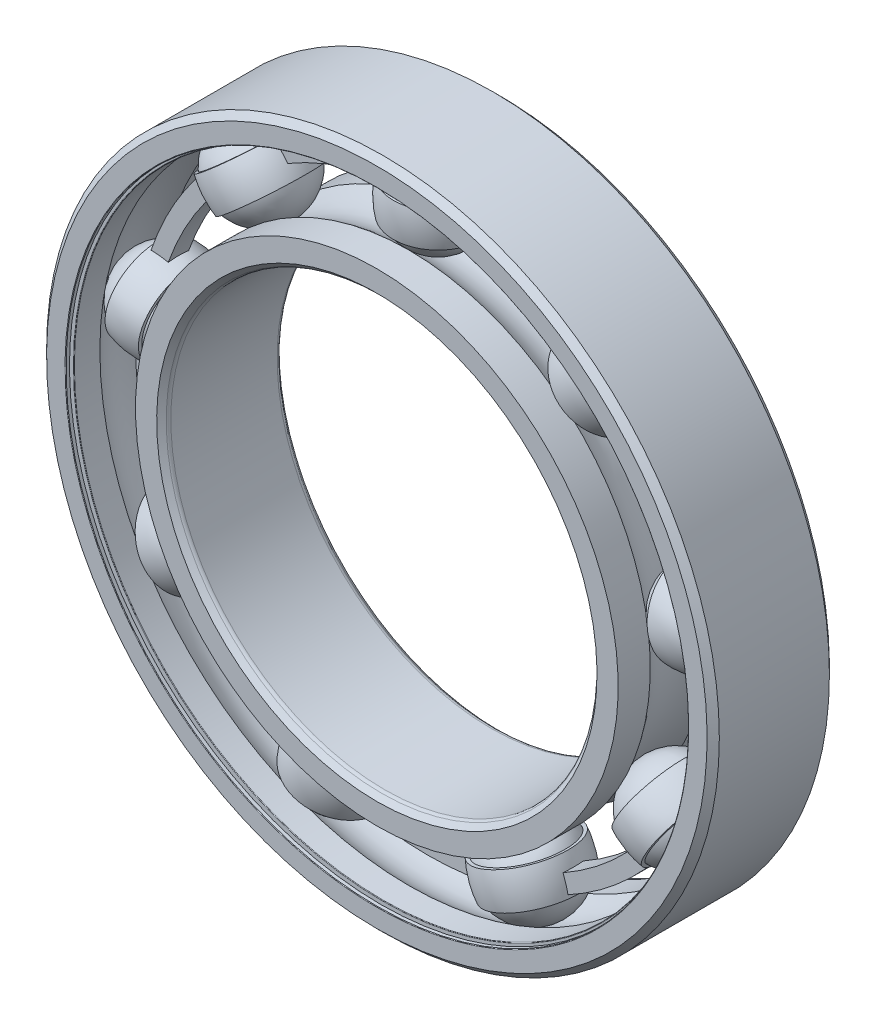
SolidWorks part; units mm, degrees
ref_plane "Front Plane" through (0, 0, 0) normal (0, 0, 1) x (1, 0, 0)
ref_plane "Top Plane" through (0, 0, 0) normal (0, 1, 0) x (1, 0, 0)
ref_plane "Right Plane" through (0, 0, 0) normal (1, 0, 0) x (0, 0, -1)
sketch "Sketch1" plane through (0, 0, 0) normal (0, 0, 1) x (1, 0, 0)
  line L0 (-27.5, 0) -> (27.5, 0) construction
  line L1 (-17.4995, 0) -> (17.4995, 0) construction
  circle A0 centre (0, 0) radius 17.4995 construction
  circle A1 centre (0, 0) radius 27.5 construction
  point P3 (0, 0)
  point P6 (0, 0)
  point P7 (0, -17.4995)
  point P11 (0, -27.5)
  point P12 (0, 17.4995)
  point P13 (0, 27.5)
  dimension "OD" = 55
  dimension "ID" = 34.999
sketch "Sketch2" plane through (0, 0, 0) normal (1, 0, 0) x (0, 0, -1)
  line L0 (-5, 27.5) -> (5, 27.5) construction
  line L1 (0, 27.5) -> (0, -27.5) construction
  line L2 (4.5, 27.5) -> (-4.5, 27.5)
  line L3 (-4.5, 27.5) -> (-5, 27)
  line L4 (-5, 27) -> (-5, 25.269)
  line L5 (-5, 25.269) -> (-2.375, 25.269)
  line L6 (5, 25.269) -> (2.375, 25.269)
  line L7 (5, 27) -> (5, 25.269)
  line L8 (4.5, 27.5) -> (5, 27)
  line L9 (0, 27.5) -> (0, 22.4997) construction
  line L10 (0, 22.4997) -> (0, 17.4995) construction
  line L11 (0, 27.5) -> (0, -27.5) construction
  line L12 (-5, 0) -> (5, 0) construction
  line L13 (5, 17.4995) -> (-5, 17.4995) construction
  line L14 (0, 26.1479) -> (0, 18.8516) construction
  line L15 (-5, -17.4995) -> (5, -17.4995) construction
  line L16 (-5, -17.5) -> (-5, 17.5) construction
  line L17 (5, 27.5) -> (5, -27.5) construction
  arc A0 (-2.375, 25.269) -> (2.375, 25.269) centre (0, 22.4997) cw
  circle A1 centre (0, 22.4997) radius 3.6482 construction
  point P14 (0, 17.4995)
  point P17 (0, 0)
  point P21 (0, 27.5)
  point P29 (0, 17.4995)
  point P30 (0, -17.4995)
  point P35 (0, 26.1479)
  dimension "Approx. Ball Dia." = 7.2964
  dimension "Width" = 10
  dimension "D1" = 45
  dimension "D2" = 0.5
  dimension "D3" = 4.75
  dimension "D4" = 2.7692
  dimension "For Shaft Diameter" = 35
  dimension "For Housing ID" = 55
sketch "Sketch3" plane through (0, 0, 0) normal (1, 0, 0) x (0, 0, -1)
  line L0 (4.5, 27.5) -> (5, 27) construction
  line L1 (5, 27) -> (5, 25.269) construction
  line L2 (5, 25.269) -> (2.375, 25.269) construction
  line L3 (-5, 25.269) -> (-2.375, 25.269) construction
  line L4 (-5, 27) -> (-5, 25.269) construction
  line L5 (-4.5, 27.5) -> (-5, 27) construction
  line L6 (4.5, 27.5) -> (-4.5, 27.5) construction
  line L7 (4.5, 27.5) -> (5, 27)
  line L8 (5, 27) -> (5, 25.269)
  line L9 (5, 25.269) -> (2.375, 25.269)
  line L10 (-5, 25.269) -> (-2.375, 25.269)
  line L11 (-5, 27) -> (-5, 25.269)
  line L12 (-4.5, 27.5) -> (-5, 27)
  line L13 (4.5, 27.5) -> (-4.5, 27.5)
  arc A0 (2.375, 25.269) -> (-2.375, 25.269) centre (0, 22.4997) ccw construction
  arc A1 (2.375, 25.269) -> (-2.375, 25.269) centre (0, 22.4997) ccw
revolve "Revolve1" add sketch "Sketch3" angle 360 about L12
sketch "Sketch8" plane through (0, 0, 0) normal (1, 0, 0) x (0, 0, -1)
  line L0 (-5, 25.269) -> (-2.375, 25.269) construction
  line L1 (-4.68, 25.269) -> (-4.5, 25.269)
  line L2 (-4.68, 25.269) -> (-4.68, 26.0127) construction
  line L3 (-4.68, 26.0127) -> (-4.5, 26.0127)
  line L4 (-4.5, 25.269) -> (-4.5, 26.0127)
  line L5 (5, 25.269) -> (2.375, 25.269) construction
  line L6 (4.5, 25.269) -> (4.68, 25.269)
  line L7 (4.5, 25.269) -> (4.5, 26.0127)
  line L8 (4.5, 26.0127) -> (4.68, 26.0127)
  line L9 (4.68, 25.269) -> (4.68, 26.0127) construction
  line L10 (-4.5, 26.0127) -> (4.5, 26.0127) construction
  line L11 (0, 27.5) -> (0, -27.5) construction
  line L12 (-4.68, 26.0127) -> (-4.68, 26.7563) construction
  line L13 (-4.68, 26.7563) -> (-4.68, 27.5) construction
  line L14 (-5, 27.5) -> (5, 27.5) construction
  line L15 (-4.68, 25.269) -> (-5, 25.269)
  line L16 (-5, 25.269) -> (-5, 25.449)
  line L17 (-5, 27) -> (-5, 25.269) construction
  line L18 (-5, 25.449) -> (-4.68, 25.449)
  line L19 (-4.68, 25.449) -> (-4.68, 26.0127)
  line L20 (4.68, 25.269) -> (5, 25.269)
  line L21 (5, 25.269) -> (5, 25.449)
  line L22 (5, 27) -> (5, 25.269) construction
  line L23 (5, 25.449) -> (4.68, 25.449)
  line L24 (4.68, 25.449) -> (4.68, 26.0127)
  point P12 (0, 26.0127)
  dimension "D1" = 9
  dimension "D2" = 0.18
revolve "Cut-Revolve1" cut sketch "Sketch8" angle 360 about L12
sketch "Sketch4" plane through (0, 0, 0) normal (1, 0, 0) x (0, 0, -1)
  line L0 (0, 27.5) -> (0, -27.5) construction
  line L1 (0, 27.5) -> (0, -27.5) construction
  line L2 (-4.5, 17.4995) -> (-5, 17.9995)
  line L3 (-5, 17.9995) -> (-5, 19.7305)
  line L5 (-5, 19.7305) -> (-2.375, 19.7305)
  line L6 (-4.5, 17.4995) -> (4.5, 17.4995)
  line L8 (4.5, 17.4995) -> (5, 17.9995)
  line L10 (5, 17.9995) -> (5, 19.7305)
  line L11 (5, 19.7305) -> (2.375, 19.7305)
  line L12 (-5, 27) -> (-5, 25.269) construction
  line L13 (4.5, 27.5) -> (5, 27) construction
  line L15 (5, -27) -> (5, 27) construction
  line L16 (4.5, 27.5) -> (4.5, -27.5) construction
  arc A1 (2.375, 19.7305) -> (-2.375, 19.7305) centre (0, 22.4997) cw
  circle A2 centre (0, 22.4997) radius 3.6482 construction
  point P1 (0, 17.4995)
revolve "Revolve2" add sketch "Sketch4" angle 360 about L12
sketch "Sketch5" plane through (0, 0, 0) normal (1, 0, 0) x (0, 0, -1)
  line L0 (-3.6482, 22.4997) -> (3.6482, 22.4997)
  arc A2 (-3.6482, 22.4997) -> (3.6482, 22.4997) centre (0, 22.4997) cw
  arc A3 (2.375, 25.269) -> (-2.375, 25.269) centre (0, 22.4997) ccw construction
revolve "Revolve3" add sketch "Sketch5" angle 360 about L0
sketch "Sketch6" plane through (0, 0, 0) normal (1, 0, 0) x (0, 0, -1)
  line L0 (-2.375, 25.269) -> (-2.375, 23.8844) construction
  line L1 (-2.375, 23.8844) -> (-2.375, 22.4997) construction
  line L2 (-2.375, 22.4997) -> (-2.375, 21.1151) construction
  line L3 (-2.375, 21.1151) -> (-2.375, 19.7305) construction
  line L4 (-5, 23.8844) -> (-4.7292, 23.8844) construction
  line L5 (-2.375, 23.8844) -> (-2.375, 21.1151) construction
  line L7 (-4.7292, 23.8844) -> (-4.4584, 23.8844) construction
  line L8 (-4.4584, 23.8844) -> (-4.1876, 23.8844) construction
  line L10 (0, 27.5) -> (0, -27.5) construction
  line L11 (0, 27.5) -> (0, -27.5) construction
  line L12 (-5, 25.269) -> (-5, 23.8844) construction
  line L13 (-3.646, 23.8844) -> (-3.3752, 23.8844) construction
  line L14 (-5, 27) -> (-5, -27) construction
  line L15 (-5, 23.8844) -> (-5, 22.4997) construction
  line L16 (-5, 22.4997) -> (-5, 21.1151) construction
  line L17 (-5, 21.1151) -> (-5, 19.7305) construction
  line L18 (-4.1876, 23.8844) -> (-3.9168, 23.8844) construction
  line L19 (-3.9168, 23.8844) -> (-3.646, 23.8844) construction
  line L20 (-3.3752, 23.8844) -> (-3.646, 23.8844)
  line L21 (-5, 21.1151) -> (-4.7292, 21.1151) construction
  line L22 (-4.7292, 21.1151) -> (-4.4584, 21.1151) construction
  line L23 (-4.4584, 21.1151) -> (-4.1876, 21.1151) construction
  line L24 (-4.1876, 21.1151) -> (-3.9168, 21.1151) construction
  line L25 (-3.9168, 21.1151) -> (-3.646, 21.1151) construction
  line L26 (-3.646, 21.1151) -> (-3.3752, 21.1151) construction
  line L27 (-3.3752, 21.1151) -> (-3.646, 21.1151)
  line L28 (-3.9168, 23.8844) -> (-3.9168, 21.1151) construction
  line L30 (-3.7814, 23.8844) -> (-3.7814, 21.1151) construction
  circle A0 centre (0, 22.4997) radius 3.6482 construction
  arc A2 (-3.646, 21.1151) -> (-3.646, 23.8844) centre (3.366, 22.4997) cw
  arc A3 (-3.3752, 23.8844) -> (-3.3752, 21.1151) centre (0, 22.4997) ccw
revolve "Revolve4" add sketch "Sketch6" angle 360 about L11
sketch "Sketch7" plane through (0, 0, 0) normal (0, 0, 1) x (1, 0, 0)
  line L0 (-3.6482, 22.4997) -> (3.6482, 22.4997) construction
  line L1 (0, 18.8516) -> (0, 26.1479) construction
  line L2 (0, 0) -> (7.6954, 21.1428) construction
  line L8 (0, 27.5) -> (0, -27.5) construction
  line L9 (14.4626, 17.2358) -> (15.3526, 18.2965)
  line L10 (0, 27.5) -> (0, -27.5) construction
  line L11 (0, 23.8844) -> (0, 22.4997)
  arc A1 (14.4626, 17.2358) -> (0, 22.4997) centre (0, 0) ccw
  arc A2 (15.3526, 18.2965) -> (0, 23.8844) centre (0, 0) ccw
  dimension "D1" = 40
  dimension "D2" = 7.2964
extrude "Boss-Extrude1" add sketch "Sketch7" along normal mid plane 1.6667
pattern_circular "CirPattern1" count 9 over 360 about axis through (0, 0, 5) along (0, 0, -1) of bodies 104 134
pattern_circular "CirPattern2" count 9 over 360 about axis through (0, 0, 5) along (0, 0, -1) of "Revolve4", "Boss-Extrude1" reverse direction yes
fillet "Fillet1" radius 0.045 4 edges at (0, -25.269, -4.5) (0, -25.449, -5) (0, -25.269, 4.5) (0, -25.449, 5)
fillet "Fillet2" radius 0.375 2 edges at (0, -17.4995, -4.5) (0, -17.4995, 4.5)
ref_plane "Plane1" through (7.6954, 21.1428, 0) normal (0.342, 0.9397, 0) x (0.9397, -0.342, 0)
sketch "Sketch9" plane through (7.6954, 21.1428, 0) normal (0.342, 0.9397, 0) x (0.9397, -0.342, 0)
  line L0 (-4.2672, -0.8333) -> (-4.2672, -2.5)
  line L1 (-4.2672, -2.5) -> (-1.851, -2.5)
  line L2 (-1.851, -2.5) -> (0, -0.9469)
  line L3 (0, -0.9469) -> (1.851, -2.5)
  line L4 (1.851, -2.5) -> (4.2672, -2.5)
  line L5 (4.2672, -2.5) -> (4.2672, -0.8333)
  line L6 (4.2672, -0.8333) -> (-4.2672, -0.8333)
  line L7 (0, -0.8333) -> (0, 0) construction
  line L8 (-4.2672, -0.8333) -> (-4.2672, 0) construction
  dimension "D1" = 1.6667
  dimension "D2" = 0.8333
  dimension "D3" = 40
extrude "Boss-Extrude2" [suppressed] add sketch "Sketch9" along normal blind 3.1922 draft 15 and the other way blind 3.1922 draft 10 separate body draft outward yes other way draft outward yes
fillet "Fillet3" [suppressed] radius 0.5
mirror "Mirror1" [suppressed] about plane through (0, 0, 0) normal (0, 0, 1) of bodies 149
pattern_circular "CirPattern3" [suppressed] count 9 over 360 about axis through (0, 0, 5) along (0, 0, -1) of bodies 158 149
equation "\"D2@Sketch2\" = \"Width@Sketch2\" * .05"
equation "\"D3@Sketch2\"=\"Width@Sketch2\" * .475"
equation "\"D4@Sketch2\" =  (  (  ( \"OD@Sketch1\" - \"Width@Sketch2\" )  / 2 )  / 3.25 )  / 2.5"
equation "\"D1@Boss-Extrude1\" = \"Width@Sketch2\" / 6"
equation "\"D1@Sketch8\"=\"Width@Sketch2\"*.9"
equation "\"D2@Sketch8\"=\"D1@Sketch8\"*.02"
equation "\"D1@Fillet1\" = \"D2@Sketch8\" * .25"
equation "\"D1@Fillet2\" = \"D2@Sketch2\" * .75"
equation "\"Approx No of Balls@CirPattern1\" = ( pi * \"OD@Sketch1\" ) * .4 / \"Approx. Ball Dia.@Sketch2\""
equation "\"D1@Sketch7\" = 360 / \"Approx No of Balls@CirPattern1\""
equation "\"D1@CirPattern2\" = \"Approx No of Balls@CirPattern1\""
equation "\"D2@Sketch7\"=\"Approx. Ball Dia.@Sketch2\""
equation "\"D2@Sketch9\" = \"D1@Boss-Extrude1\" * .5"
equation "\"D1@Sketch9\"=\"D2@Sketch9\"*2"
equation "\"D1@Boss-Extrude2\"=\"Approx. Ball Dia.@Sketch2\"*.4375"
equation "\"D2@Boss-Extrude2\"=\"D1@Boss-Extrude2\""
equation "\"D1@CirPattern3\" = \"Approx No of Balls@CirPattern1\""
equation "\"D1@Fillet3\"=\"D1@Sketch9\" * .3"
